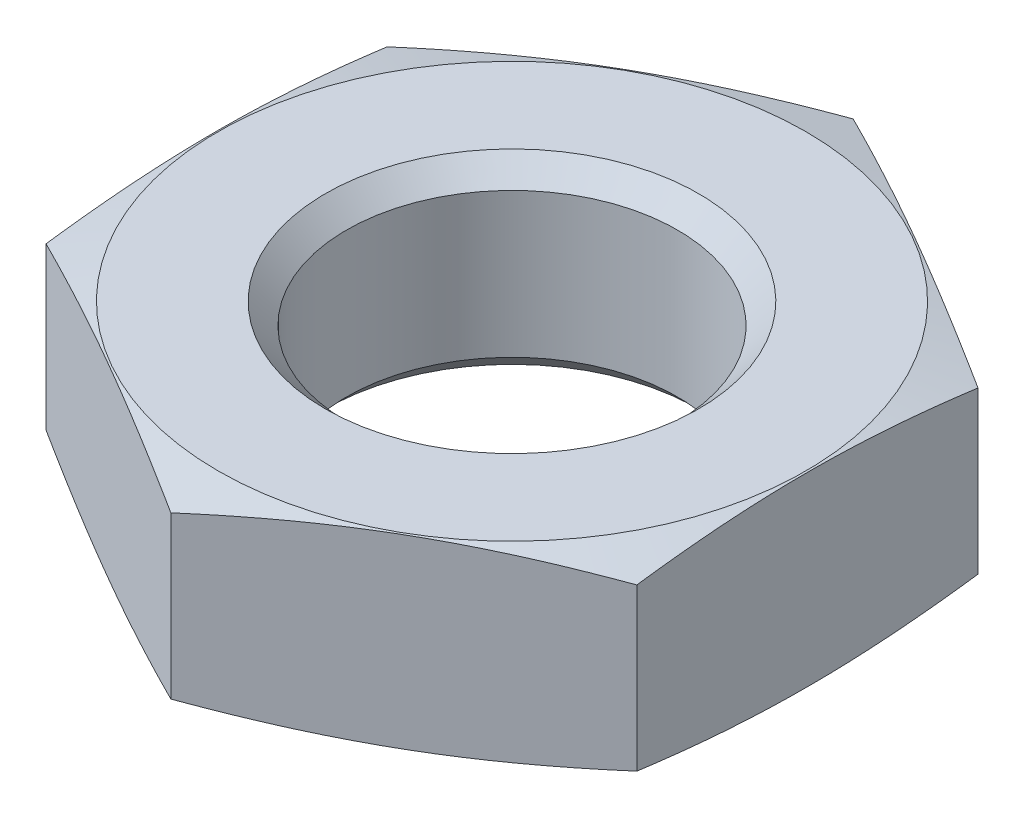
SolidWorks part; units mm, degrees
ref_plane "Front Plane" through (0, 0, 0) normal (0, 0, 1) x (1, 0, 0)
ref_plane "Top Plane" through (0, 0, 0) normal (0, 1, 0) x (1, 0, 0)
ref_plane "Right Plane" through (0, 0, 0) normal (1, 0, 0) x (0, 0, -1)
sketch "Sketch1" plane through (0, 0, 0) normal (0, 0, 1) x (1, 0, 0)
  line L0 (0, 0) -> (9.45, 0)
  line L1 (9.45, 0) -> (20.6462, -3)
  line L2 (20.6462, -3) -> (9.45, -6)
  line L3 (9.45, -6) -> (0, -6)
  line L4 (0, -6) -> (0, 0)
  line L5 (0, -6) -> (0, 0) construction
revolve "Revolve1" add sketch "Sketch1" angle 360 about L5
sketch "Sketch2" plane through (0, 0, 0) normal (0, 1, 0) x (1, 0, 0)
  line L0 (-38, 38) -> (-38, -38)
  line L1 (-38, -38) -> (38, -38)
  line L2 (38, -38) -> (38, 38)
  line L3 (38, 38) -> (-38, 38)
  line L4 (-9.5, -5.4848) -> (0, -10.9697)
  line L5 (0, -10.9697) -> (9.5, -5.4848)
  line L6 (9.5, -5.4848) -> (9.5, 5.4848)
  line L7 (9.5, 5.4848) -> (0, 10.9697)
  line L8 (0, 10.9697) -> (-9.5, 5.4848)
  line L9 (-9.5, 5.4848) -> (-9.5, -5.4848)
extrude "Cut-Extrude1" cut sketch "Sketch2" along normal blind 7 and the other way blind 7
sketch "Sketch3" plane through (0, 0, 0) normal (0, 0, 1) x (1, 0, 0)
  line L0 (0, 0) -> (6, 0)
  line L1 (6, 0) -> (5.3235, -0.6765)
  line L2 (5.3235, -0.6765) -> (5.3235, -5.3235)
  line L3 (5.3235, -5.3235) -> (6, -6)
  line L4 (6, -6) -> (0, -6)
  line L5 (0, -6) -> (0, 0)
  line L6 (0, -6) -> (0, 0) construction
revolve "Cut-Revolve1" cut sketch "Sketch3" angle 360 about L6 reverse direction yes
cosmetic thread "Cosmetic Thread1" parameters "D1"=6, "D2"=12
ref_plane "Plane1" through (0, -3, 0) normal (0, 1, 0) x (1, 0, 0)
ref_plane "2CYL XY" through (0, -3, 0) normal (0, 1, 0) x (1, 0, 0)
ref_plane "2CYL XZ" through (0, 0, 0) normal (0, 0, 1) x (1, 0, 0)
ref_plane "2CYL YZ" through (0, 0, 0) normal (1, 0, 0) x (0, 0, -1)
ref_axis "2CYL X" through (-80.9, -3, 0) along (1, 0, 0)
ref_axis "2CYL Y" through (0, -3, 50) along (0, 0, -1)
ref_axis "2CYL Z" through (0, 50, 0) along (0, -1, 0)
sketch3d "2CYL"
  point P0 (0, -3, 0)
ref_plane "din439b_punkt XY" through (0, 0, 0) normal (0, 1, 0) x (1, 0, 0)
ref_plane "din439b_punkt XZ" through (0, 0, 0) normal (0, 0, 1) x (1, 0, 0)
ref_plane "din439b_punkt YZ" through (0, 0, 0) normal (1, 0, 0) x (0, 0, -1)
ref_axis "din439b_punkt X" through (-80.9, 0, 0) along (1, 0, 0)
ref_axis "din439b_punkt Y" through (0, 0, 50) along (0, 0, -1)
ref_axis "din439b_punkt Z" through (0, 50, 0) along (0, -1, 0)
sketch3d "din439b_punkt"
  point P0 (0, 0, 0)
